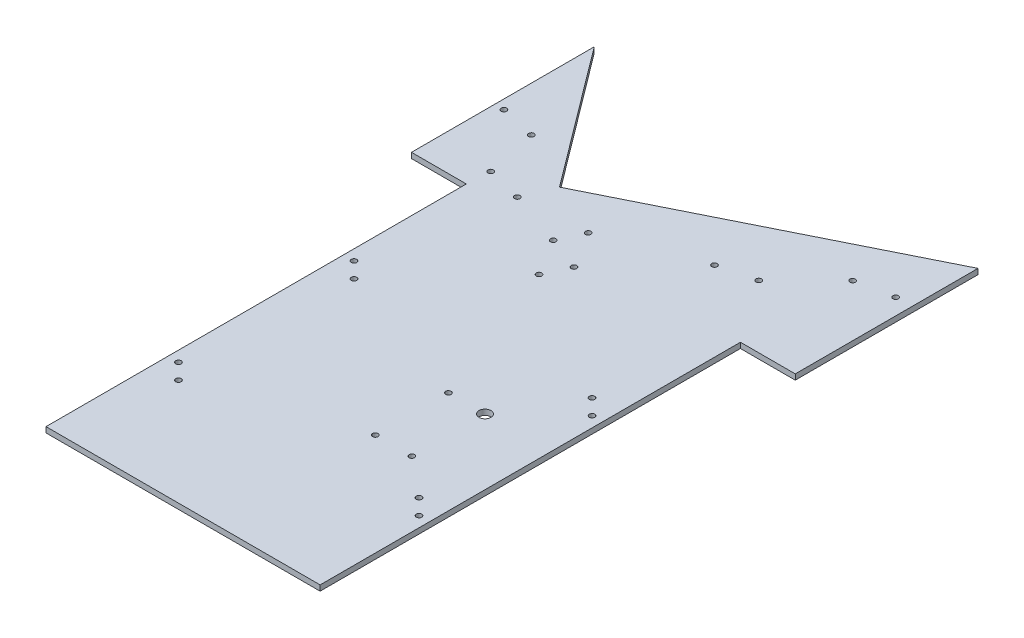
SolidWorks part; units mm, degrees
ref_plane "Front Plane" through (0, 0, 0) normal (0, 0, 1) x (1, 0, 0)
ref_plane "Top Plane" through (0, 0, 0) normal (0, 1, 0) x (1, 0, 0)
ref_plane "Right Plane" through (0, 0, 0) normal (1, 0, 0) x (0, 0, -1)
sketch "Sketch1" plane through (0, 0, 0) normal (0, 1, 0) x (1, 0, 0)
  line L1 (-75, -100) -> (75, -100)
  line L2 (-75, -100) -> (-75, 100)
  line L3 (-75, 100) -> (75, 100)
  line L4 (75, -100) -> (75, 100)
  line L5 (-75, -100) -> (75, 100) construction
  line L6 (-75, 100) -> (75, -100) construction
  circle A0 centre (-69.2426, 62.7961) radius 1.5
  circle A1 centre (-60.7574, 54.3108) radius 1.5
  circle A2 centre (60.7574, 63.0348) radius 1.5
  circle A3 centre (69.2426, 54.5495) radius 1.5
  circle A4 centre (-69.2426, -33.2742) radius 1.5
  circle A5 centre (-60.7574, -41.7595) radius 1.5
  circle A6 centre (60.7574, -31.6419) radius 1.5
  circle A7 centre (69.2426, -40.1271) radius 1.5
  circle A8 centre (19.1, 26.1028) radius 1.5
  circle A9 centre (39.1, 26.1028) radius 3.2638
  circle A10 centre (39.1, -13.8972) radius 1.5
  circle A11 centre (19.1, -13.8972) radius 1.5
  point P0 (0, 0)
  dimension "D1" = 150
  dimension "D2" = 200
extrude "Boss-Extrude1" add sketch "Sketch1" along normal blind 3
sketch "Sketch2" plane through (0, 3, 0) normal (0, 1, 0) x (1, 0, 0)
  line L8 (-75, 100) -> (-75, 130)
  line L9 (-75, 130) -> (-105, 130)
  line L10 (-105, 130) -> (-105, 230)
  line L11 (-105, 230) -> (-48, 154)
  line L12 (-48, 154) -> (105, 230)
  line L13 (105, 230) -> (105, 130)
  line L14 (105, 130) -> (75, 130)
  line L15 (75, 130) -> (75, 100)
  line L20 (-75, 100) -> (75, 100)
  circle A0 centre (-12.2136, 106.9838) radius 1.5
  circle A1 centre (-6.1619, 120.0749) radius 1.5
  circle A2 centre (-18.4792, 140.175) radius 1.5
  circle A3 centre (-24.5309, 127.0839) radius 1.5
  circle A4 centre (31.34, 159.4445) radius 1.5
  circle A5 centre (50.7426, 164.2965) radius 1.5
  circle A6 centre (76.5366, 189.8832) radius 1.5
  circle A7 centre (96.1557, 193.7679) radius 1.5
  circle A8 centre (-54.8196, 137.7444) radius 1.5
  circle A9 centre (-74.2221, 142.5964) radius 1.5
  circle A10 centre (-80.4244, 170.9971) radius 1.5
  circle A11 centre (-99.9157, 175.4791) radius 1.5
  dimension "D2" = 100
  dimension "D3" = 27
  dimension "D4" = 30
  dimension "D1" = 30
  dimension "D5" = 24
extrude "Boss-Extrude3" add sketch "Sketch2" against normal blind 3
